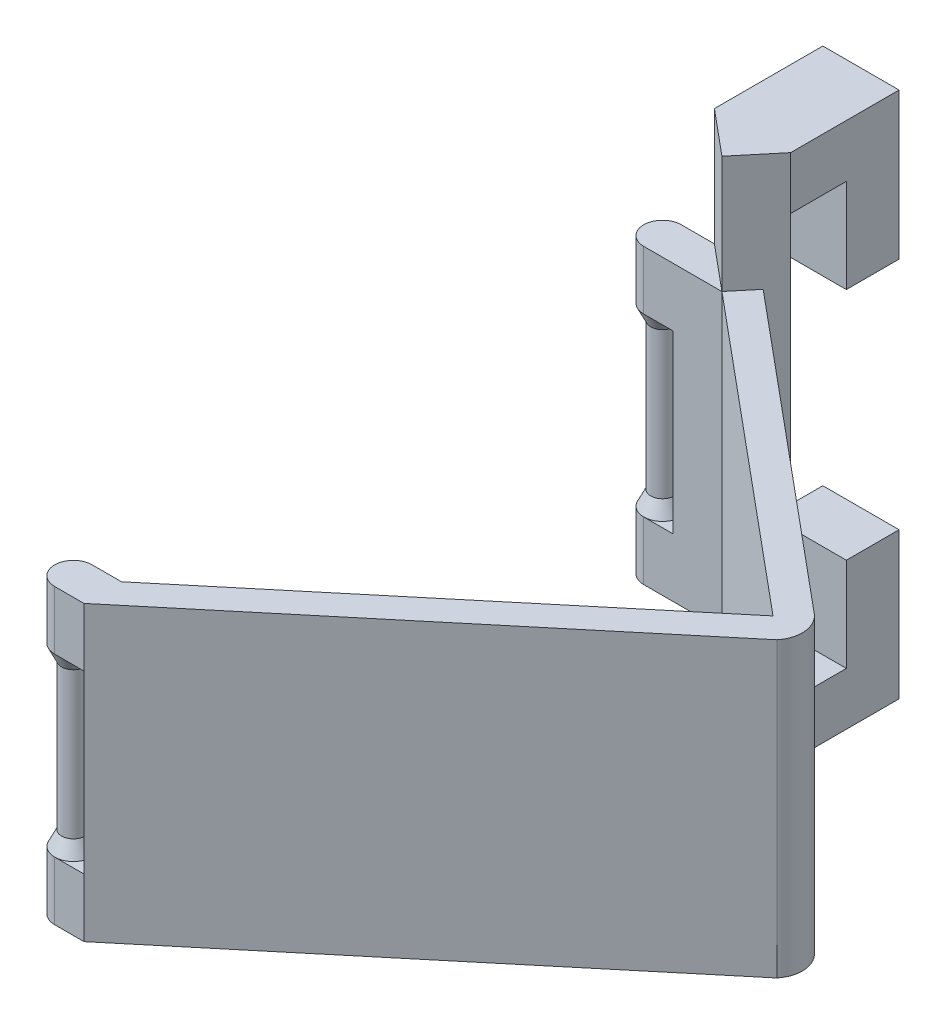
SolidWorks part; units mm, degrees
ref_plane "前视基准面" through (0, 0, 0) normal (0, 0, 1) x (1, 0, 0)
ref_plane "上视基准面" through (0, 0, 0) normal (0, 1, 0) x (1, 0, 0)
ref_plane "右视基准面" through (0, 0, 0) normal (1, 0, 0) x (0, 0, -1)
sketch "草图1" plane through (0, 0, 0) normal (0, 1, 0) x (1, 0, 0)
  line L0 (0, 0) -> (0, 50)
  line L1 (0, 0) -> (-0.664, -50.5533)
  line L2 (0, 0) -> (60, 0)
  line L3 (60, 0) -> (-0.664, -50.5533)
  line L4 (0, 50) -> (60, 0)
  line L5 (60, 0) -> (63.2009, 3.8411)
  line L6 (63.2009, 3.8411) -> (7.8102, 50)
  line L7 (60, 0) -> (63.8411, -3.2009)
  line L8 (63.8411, -3.2009) -> (7.6822, -50)
  line L9 (0, 50) -> (7.8102, 50)
  line L11 (7.6822, -50) -> (-0.664, -56.9551)
  line L12 (-0.664, -56.9551) -> (-0.664, -50.5533)
  arc A0 (63.2009, 3.8411) -> (63.8411, -3.2009) centre (60, 0) cw
extrude "凸台-拉伸1" add sketch "草图1" along normal blind 50 contours L3 L8 L7 | A0 L5 L7 | L9 L4 L5 L6 region at (32.7161, 0, -25.9475) region at (30.6381, 0, 27.7019) region at (62.9887, 0, -0.2717)
sketch "草图3" plane through (27.7911, 0, -33.3493) normal (0.6402, 0, -0.7682) x (-0.7682, 0, -0.6402)
  line L0 (-46.0933, 25) -> (26.0092, 25) construction
  line L1 (-46.0933, 50) -> (-46.0933, 0) construction
  line L2 (26.0092, 50) -> (26.0092, 0) construction
ref_plane "基准面1" through (0, 25, 0) normal (0, -1, 0) x (-0.7682, 0, -0.6402)
sketch "草图4" plane through (0, 50, 0) normal (0, 1, 0) x (1, 0, 0)
  line L0 (0, 50) -> (7.6822, 43.5982)
  line L1 (0, 50) -> (60, 0) construction
  line L2 (7.6822, 43.5982) -> (10.8831, 47.4393)
  line L3 (63.2009, 3.8411) -> (7.8102, 50) construction
  line L4 (10.8831, 47.4393) -> (7.8102, 50)
  line L5 (7.8102, 50) -> (0, 50)
  line L6 (7.8102, 50) -> (19.6167, 50)
  line L7 (10.8831, 47.4393) -> (13.0171, 50)
  line M4 (63.2009, 3.8411) -> (7.8102, 50)
  line M5 (7.8102, 50) -> (0, 50)
  line M6 (0, 50) -> (60, 0)
extrude "凸台-拉伸3" add sketch "草图4" along normal blind 20 and the other way blind 50 contours L2 M6 M4 M5 | L7 L6 M4 region at (6.2006, 50, -47.6222) region at (10.5702, 50, -49.1464)
sketch "草图5" plane through (0, 0, -50) normal (0, 0, -1) x (-1, 0, 0)
  line L0 (-13.0171, 70) -> (-13.0171, 61)
  line L1 (-13.0171, 0) -> (-13.0171, 70) construction
  line L2 (-13.0171, 61) -> (0, 61)
  line L3 (0, 70) -> (0, 0) construction
  line L4 (0, 61) -> (0, 70)
  line L5 (0, 70) -> (-13.0171, 70)
extrude "凸台-拉伸4" add sketch "草图5" along normal blind 18.5
sketch "草图6" plane through (0, 61, 0) normal (0, -1, 0) x (1, 0, 0)
  line L0 (0, -68.5) -> (0, -59.5)
  line L1 (0, -68.5) -> (0, -50) construction
  line L2 (13.0171, -68.5) -> (0, -68.5) construction
  line L3 (0, -59.5) -> (13.0171, -59.5)
  line L4 (13.0171, -68.5) -> (13.0171, -50) construction
  line L5 (13.0171, -59.5) -> (13.0171, -68.5)
  line L6 (13.0171, -68.5) -> (0, -68.5)
extrude "凸台-拉伸5" add sketch "草图6" along normal blind 16
mirror "镜向4" about plane through (0, 25, 0) normal (0, -1, 0) of "凸台-拉伸5", "凸台-拉伸3", "凸台-拉伸4"
sketch "草图7" plane through (0, 50, 0) normal (0, 1, 0) x (1, 0, 0)
  line L0 (-0.664, -53.7542) -> (-5.664, -53.7542)
  line L1 (-0.664, -56.9551) -> (-0.664, -50.5533) construction
  line L2 (-5.664, -53.7542) -> (-5.664, 89.3377)
sketch "草图8" plane through (0, 50, 0) normal (0, 1, 0) x (1, 0, 0)
  line L0 (-0.664, -50.5533) -> (-0.664, 65.3859)
  line L1 (7.6822, 43.5982) -> (-0.664, 43.5982)
  line L2 (-0.664, 43.5982) -> (-0.664, 50)
  line L3 (-0.664, 50) -> (0, 50)
  line L4 (0, 50) -> (7.6822, 43.5982)
extrude "凸台-拉伸6" add sketch "草图8" against normal blind 50 contours L1 L2 L3 L4
sketch "草图9" plane through (0, 0, 0) normal (0, -1, 0) x (1, 0, 0)
  line L0 (-0.664, 56.9551) -> (-5.664, 56.9551)
  line L1 (-0.664, 50.5533) -> (-5.664, 50.5533)
  line L2 (-5.664, 53.7542) -> (-5.664, -89.3377) construction
  line L3 (-0.664, 56.9551) -> (-0.664, 50.5533)
  line L4 (-5.664, 56.9551) -> (-5.664, 50.5533)
  arc A0 (-5.664, 56.9551) -> (-5.664, 50.5533) centre (-5.664, 53.7542) ccw
  line M5 (-0.664, 56.9551) -> (-0.664, 50.5533)
extrude "凸台-拉伸7" add sketch "草图9" against normal blind 10 contours L0 L4 L1 M5 | L4 A0 region at (-3.164, 0, 53.7542) region at (-7.0225, 0, 53.7542)
sketch "草图10" plane through (0, 0, 0) normal (0, -1, 0) x (1, 0, 0)
  line L0 (-0.664, -43.5982) -> (-5.664, -43.5982)
  line L1 (-5.664, 53.7542) -> (-5.664, -89.3377) construction
  line L2 (-0.664, -50) -> (-5.664, -50)
  line L3 (-5.664, -43.5982) -> (-5.664, -50)
  arc A0 (-5.664, -43.5982) -> (-5.664, -50) centre (-5.664, -46.7991) ccw
  line M3 (-0.664, -43.5982) -> (-0.664, -50)
extrude "凸台-拉伸8" add sketch "草图10" against normal blind 10 contours L0 L3 L2 M3 | L3 A0 region at (-3.164, 0, -46.7991) region at (-7.0225, 0, -46.7991)
mirror "镜向5" about plane through (0, 25, 0) normal (0, -1, 0) of "凸台-拉伸8", "凸台-拉伸7"
sketch "草图11" plane through (0, 40, 0) normal (0, -1, 0) x (1, 0, 0)
  circle A0 centre (-5.664, 53.7542) radius 2
extrude "凸台-拉伸9" add sketch "草图11" along normal blind 30
ref_plane "基准面3" through (0, 0, 53.7542) normal (0, 0, -1) x (-1, 0, 0)
sketch "草图14" plane through (0, 0, 53.7542) normal (0, 0, -1) x (-1, 0, 0)
  line L5 (7.664, 10) -> (8.8649, 10)
  line L6 (7.664, 10) -> (7.664, 12.5)
  line L7 (7.664, 10) -> (7.664, 40) construction
  line L8 (7.664, 12.5) -> (8.8649, 10)
ref_axis "基准轴2" through (-5.664, 10, 53.7542) along (0, 1, 0)
revolve "旋转1" add sketch "草图14" angle 360 about axis through (-5.664, 10, 53.7542) along (0, 1, 0) region at (-8.0643, 10.8333, 53.7542)
mirror "镜向6" about plane through (0, 25, 0) normal (0, -1, 0) of "旋转1"
sketch "草图15" plane through (0, 10, 0) normal (0, 1, 0) x (1, 0, 0)
  circle A0 centre (-5.664, 46.7991) radius 2
extrude "凸台-拉伸10" add sketch "草图15" along normal blind 30
sketch "草图16" plane through (0, 0, 0) normal (0, -1, 0) x (1, 0, 0)
  line L0 (-5.664, -46.7991) -> (2.4555, -46.7991)
ref_plane "基准面4" through (0, 0, -46.7991) normal (0, 0, 1) x (1, 0, 0)
ref_axis "基准轴3" through (-5.664, 40, -46.7991) along (0, -1, 0)
sketch "草图17" plane through (0, 0, -46.7991) normal (0, 0, 1) x (1, 0, 0)
  line L0 (-7.664, 10) -> (-7.664, 12.5)
  line L1 (-5.664, 10) -> (-8.8649, 10) construction
  line L2 (-7.664, 12.5) -> (-8.8649, 10)
  line L3 (-8.8649, 10) -> (-7.664, 10)
revolve "旋转2" add sketch "草图17" angle 360 about axis through (-5.664, 40, -46.7991) along (0, -1, 0)
mirror "镜向7" about plane through (0, 25, 0) normal (0, -1, 0) of "旋转2"
